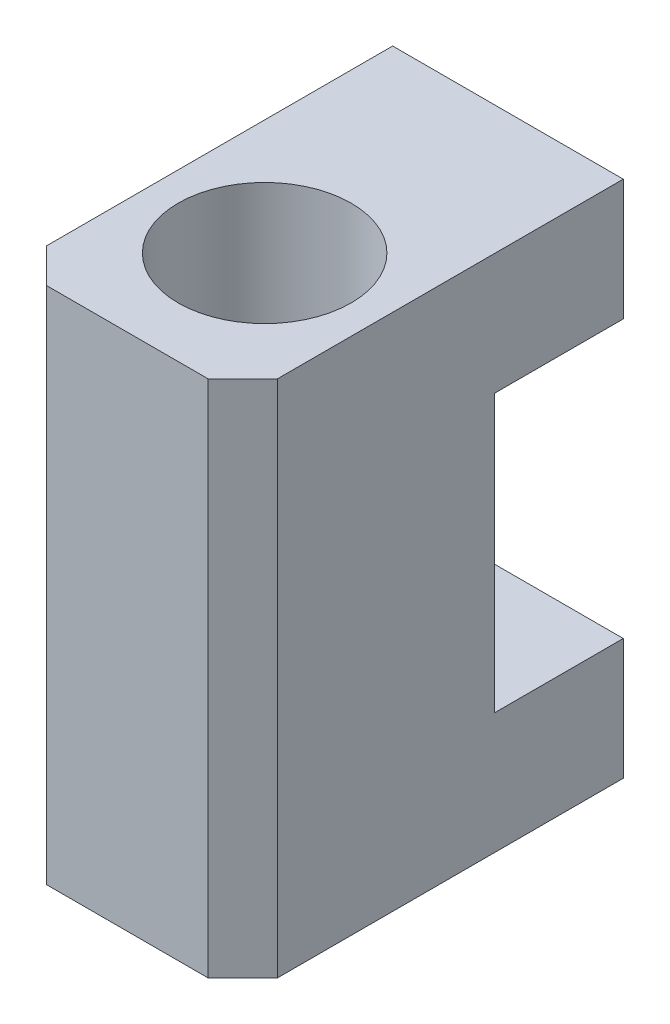
SolidWorks part; units mm, degrees
material "6061-T4 (SS)"
ref_plane "Piano frontale" through (0, 0, 0) normal (0, 0, 1) x (1, 0, 0)
ref_plane "Piano superiore" through (0, 0, 0) normal (0, 1, 0) x (1, 0, 0)
ref_plane "Piano destro" through (0, 0, 0) normal (1, 0, 0) x (0, 0, -1)
sketch "Schizzo1" plane through (0, 0, 0) normal (0, 0, 1) x (1, 0, 0)
  line L1 (0, 0) -> (20, 0)
  line L2 (0, 0) -> (0, 45)
  line L3 (0, 45) -> (20, 45)
  line L4 (20, 0) -> (20, 45)
  dimension "D1" = 45
  dimension "D2" = 20
extrude "Estrusione-Estrusione1" add sketch "Schizzo1" against normal blind 33
sketch "Schizzo2" plane through (0, 0, 0) normal (0, -1, 0) x (1, 0, 0)
  line L0 (10, 0) -> (10, -33) construction
  line L1 (0, 0) -> (20, 0) construction
  line L2 (0, -33) -> (20, -33) construction
  circle A0 centre (10, -11.9) radius 7.5
  point P6 (10, -11.9)
  dimension "D2" = 15
  dimension "D1" = 21.1
extrude "Taglio-Estrusione1" cut sketch "Schizzo2" against normal through all
sketch "Schizzo3" plane through (0, 0, -33) normal (0, 0, -1) x (-1, 0, 0)
  line L0 (0, 6) -> (-20, 6) construction
  line L1 (0, 45) -> (0, 0) construction
  line L2 (-20, 0) -> (-20, 45) construction
  line L3 (0, 22.5) -> (-20, 22.5) construction
  line L4 (0, 0) -> (-20, 0) construction
  line L5 (0, 39) -> (-20, 39) construction
  line L6 (-10, 0) -> (-10, 45) construction
  line L7 (-20, 45) -> (0, 45) construction
  point P16 (-10, 6)
  point P17 (-10, 39)
  dimension "D1" = 6
hole_wizard "Foro Ø4.0 (4)-1" positions "Schizzo3D1" profile "Schizzo4" hole size "Ø4.0" standard "ISO"
sketch3d "Schizzo3D1"
  point P0 (10, 6, -33)
  point P3 (10, 39, -33)
sketch "Schizzo4" plane through (10, 6, -33) normal (1, 0, 0) x (0, 1, 0)
  line L0 (0, 0) -> (0, 11.2017)
  line L1 (0, 11.2017) -> (2, 10)
  line L2 (2, 10) -> (2, 0)
  line L5 (2, 0) -> (0, 0)
  line L10 (0, 11.2017) -> (-2, 10) construction
  line L11 (0, -6.35) -> (0, 107.95) construction
  dimension "Hole Dia." = 4
  dimension "Hole Depth" = 10
  dimension "Drill Angle" = 118
ref_axis "Assi1" through (10, 45, -11.9) along (0, -1, 0)
chamfer "Smusso1" distance 3 angle 45 2 edges at (0, 22.5, 0) (20, 22.5, 0)
sketch "Schizzo7" plane through (0, 0, 0) normal (-1, 0, 0) x (0, 0, 1)
  line L0 (-33, 34.5) -> (-21.854, 34.5)
  line L1 (-33, 0) -> (-33, 45) construction
  line L2 (-33, 22.5) -> (0, 22.5) construction
  line L3 (0, 45) -> (0, 0) construction
  line L4 (-21.854, 34.5) -> (-21.854, 10.5)
  line L5 (-33, 34.5) -> (-33, 10.5)
  line L6 (-33, 10.5) -> (-21.854, 10.5)
  point P11 (-21.854, 22.5)
  dimension "D1" = 12
extrude "Taglio-Estrusione4" cut sketch "Schizzo7" against normal blind 26
